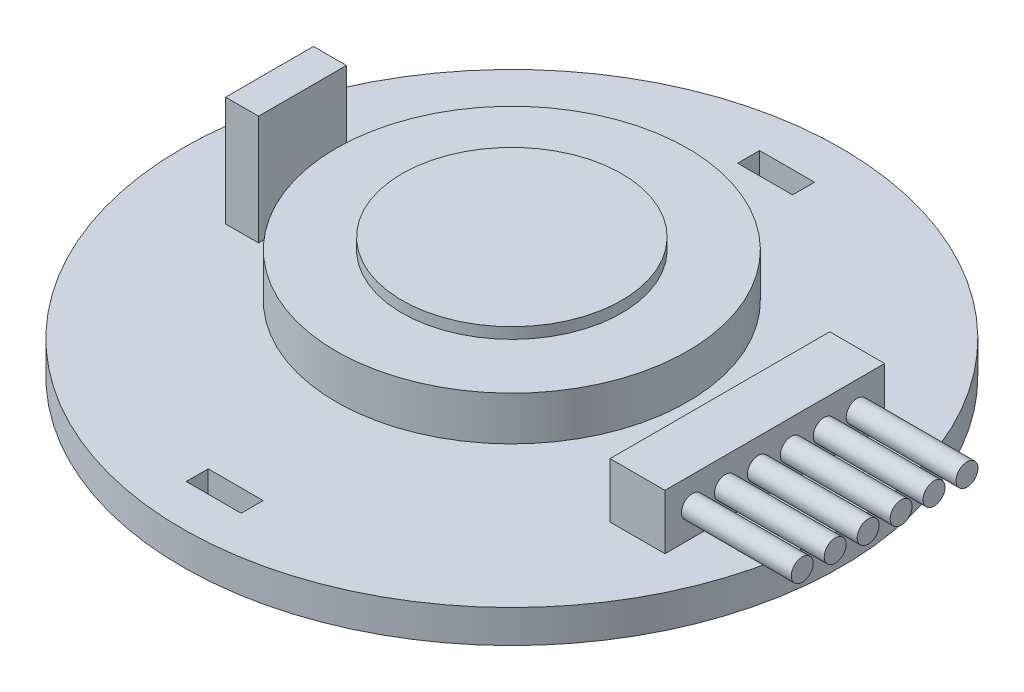
SolidWorks part; units mm, degrees
ref_plane "Front Plane" through (0, 0, 0) normal (0, 0, 1) x (1, 0, 0)
ref_plane "Top Plane" through (0, 0, 0) normal (0, 1, 0) x (1, 0, 0)
ref_plane "Right Plane" through (0, 0, 0) normal (1, 0, 0) x (0, 0, -1)
sketch "Sketch1" plane through (0, 0, 0) normal (0, 0, 1) x (1, 0, 0)
  line L0 (0.0301, -4.4219) -> (1.2301, -4.4219)
  line L1 (1.2301, -4.4219) -> (1.2301, -0.4219)
  line L2 (1.2301, -0.4219) -> (15.0301, -0.4219)
  line L3 (15.0301, -0.4219) -> (15.0301, 1.0781)
  line L4 (15.0301, 1.0781) -> (1.2301, 1.0781)
  line L5 (1.2301, 1.0781) -> (1.0301, 2.0781)
  line L6 (1.0301, 2.0781) -> (1.0301, 2.5781)
  line L7 (1.0301, 2.5781) -> (8.0301, 2.5781)
  line L8 (8.0301, 2.5781) -> (8.0301, 4.5781)
  line L9 (8.0301, 4.5781) -> (5.0301, 4.5781)
  line L10 (5.0301, 4.5781) -> (5.0301, 5.0781)
  line L11 (5.0301, 5.0781) -> (0.0301, 5.0781)
  line L12 (0.0301, 5.0781) -> (0.0301, -4.4219)
  dimension "D1" = 15
  dimension "D2" = 1.5
  dimension "D3" = 2
  dimension "D4" = 0.5
  dimension "D5" = 0.2
  dimension "D6" = 1
  dimension "D7" = 0.5
  dimension "D8" = 4
  dimension "D9" = 5
  dimension "D10" = 9.5
  dimension "D11" = 1
  dimension "D12" = 1.2
  dimension "D13" = 3
revolve "Revolve1" add sketch "Sketch1" angle 360 about L12
sketch "Sketch2" plane through (0, -0.4219, 0) normal (0, -1, 0) x (1, 0, 0)
  line L1 (-1.742, -13.05) -> (0.758, -13.05)
  line L2 (-1.742, -13.05) -> (-1.742, -12.05)
  line L3 (-1.742, -12.05) -> (0.758, -12.05)
  line L4 (0.758, -13.05) -> (0.758, -12.05)
  line L5 (-1.742, 12.05) -> (0.758, 12.05)
  line L6 (-1.742, 12.05) -> (-1.742, 13.05)
  line L7 (-1.742, 13.05) -> (0.758, 13.05)
  line L8 (0.758, 12.05) -> (0.758, 13.05)
  dimension "D1" = 1
  dimension "D2" = 2.5
  dimension "D3" = 1
  dimension "D4" = 2.5
  dimension "D5" = 24.1
  dimension "D6" = 12.05
extrude "Cut-Extrude1" cut sketch "Sketch2" against normal up to next
sketch "Sketch3" plane through (0, 1.0781, 0) normal (0, 1, 0) x (1, 0, 0)
  line L1 (-11, -2) -> (-9.5, -2)
  line L2 (-11, -2) -> (-11, 2)
  line L3 (-11, 2) -> (-9.5, 2)
  line L4 (-9.5, -2) -> (-9.5, 2)
  line L5 (9.5, -5) -> (12, -5)
  line L6 (9.5, -5) -> (9.5, 5)
  line L7 (9.5, 5) -> (12, 5)
  line L8 (12, -5) -> (12, 5)
  dimension "D1" = 4
  dimension "D2" = 1.5
  dimension "D3" = 2
  dimension "D4" = 9.5
  dimension "D5" = 2.5
  dimension "D6" = 10
  dimension "D7" = 5
  dimension "D8" = 9.5
extrude "Boss-Extrude1" add sketch "Sketch3" along normal blind 5 contours L3 L4 L1 L2
extrude "Boss-Extrude2" add sketch "Sketch3<3>" along normal blind 2.5 contours L6 L7 L8 L5
sketch "Sketch3<3>" plane through (0, 1.0781, 0) normal (0, 1, 0) x (1, 0, 0) same geometry as "Sketch3"
sketch "Sketch5" plane through (12, 0, 0) normal (1, 0, 0) x (0, 0, -1)
  line L0 (-5, 3.5781) -> (5, 3.5781) construction
  line L1 (-5, 3.5781) -> (-5, 1.0781) construction
  circle A0 centre (-3.75, 2.3281) radius 0.5
  circle A1 centre (-2.25, 2.3281) radius 0.5
  circle A2 centre (-0.75, 2.3281) radius 0.5
  circle A3 centre (0.75, 2.3281) radius 0.5
  circle A4 centre (2.25, 2.3281) radius 0.5
  circle A5 centre (3.75, 2.3281) radius 0.5
  dimension "D1" = 1
  dimension "D3" = 6
  dimension "D4" = 1.25
  dimension "D2" = 1.25
extrude "Boss-Extrude4" add sketch "Sketch5" along normal blind 5
